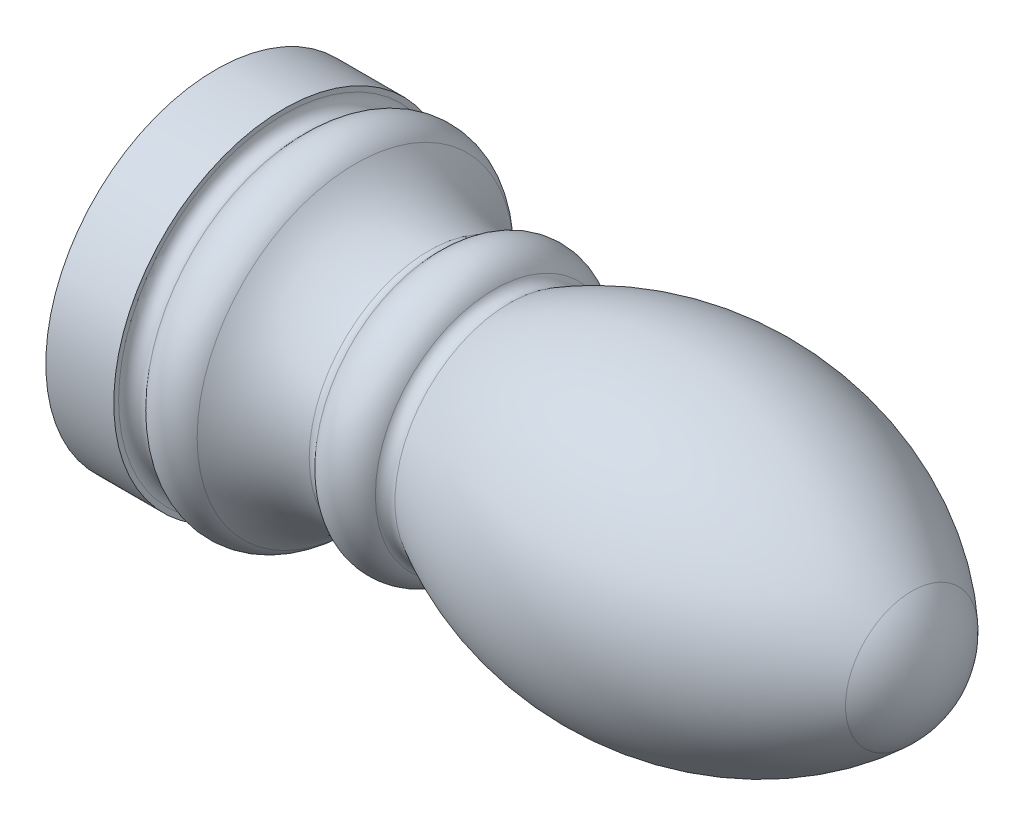
SolidWorks part; units mm, degrees
material "6061-T6 (SS)"
ref_plane "Front" through (0, 0, 0) normal (0, 0, 1) x (1, 0, 0)
ref_plane "Top" through (0, 0, 0) normal (0, 1, 0) x (1, 0, 0)
ref_plane "Right" through (0, 0, 0) normal (1, 0, 0) x (0, 0, -1)
sketch "Sketch1" plane through (0, 0, 0) normal (0, 0, 1) x (1, 0, 0)
  line L0 (0, 0) -> (0, -7.5)
  line L1 (0, -7.5) -> (3, -7.5)
  line L2 (0, 0) -> (-8.1317, 0) construction
  line L3 (0, 0) -> (32, 0)
  line L4 (3, -7.5) -> (3, -7.2856)
  line L6 (3.883, -6.9642) -> (1.6828, -4.3421) construction
  line L8 (9.8509, -5.4642) -> (8.7603, -4.1644) construction
  arc A0 (3, -7.2856) -> (3.883, -6.9642) centre (3.5, -7.2856) cw
  arc A1 (3.883, -6.9642) -> (6.1649, -6.9832) centre (5.0321, -6) ccw
  arc A3 (9.8509, -5.4642) -> (12.299, -5.25) centre (11, -4.5) ccw
  arc A5 (12.9766, -5.0639) -> (12.299, -5.25) centre (12.7321, -5.5) ccw
  arc A6 (6.1649, -6.9832) -> (9.4154, -5.2883) centre (9.941, -10.2606) cw
  arc A7 (9.4154, -5.2883) -> (9.8509, -5.4642) centre (9.4679, -5.7856) cw
  arc A8 (32, 0) -> (30.7292, -2.9243) centre (28, 0) cw
  arc A9 (30.7292, -2.9243) -> (12.9766, -5.0639) centre (20.3886, 8.1556) cw
  dimension "D2" = 4
  dimension "D6" = 14
  dimension "D7" = 1.5
  dimension "D4" = 0.5
  dimension "D8" = 40
  dimension "D10" = 1.5
  dimension "D11" = 5
  dimension "D9" = 12
  dimension "D13" = 10
  dimension "D1" = 15
  dimension "D3" = 32
  dimension "D5" = 3
  dimension "D12" = 21
revolve "Revolve1" add sketch "Sketch1" angle 360 about L2
sketch "Sketch2" plane through (0, 0, 0) normal (0, 1, 0) x (1, 0, 0)
  line L0 (31.6383, 2) -> (21.4481, 2)
  line L1 (0, 0) -> (-2.4973, 0) construction
  line L2 (0, 7.5) -> (0, -7.5) construction
  arc A0 (21.4481, 2) -> (14, 5.5877) centre (21.4481, 11.525) cw
  arc A1 (30.7292, 2.9243) -> (12.9766, 5.0639) centre (20.3886, -8.1556) ccw construction
  dimension "D3" = 19.05
  dimension "D1" = 4
  dimension "D2" = 14
extrude "Cut-Extrude1" [suppressed] cut sketch "Sketch2" against normal through all and the other way through all flip side to cut
mirror "Mirror1" [suppressed] about plane through (0, 0, 0) normal (0, 0, 1)
sketch "Sketch3" plane through (0, 0, 0) normal (0, 0, 1) x (1, 0, 0)
  line L0 (30.4335, 1.25) -> (31.7997, 1.25)
  line L2 (14, 5.5877) -> (19.3859, 1.8165)
  line L4 (0, 0) -> (8.1984, 0) construction
  line L5 (0, 7.5) -> (0, -7.5) construction
  arc A1 (30.7292, 2.9243) -> (12.9766, 5.0639) centre (20.3886, -8.1556) ccw construction
  arc A2 (22.0395, 3.8333) -> (24.3113, 4.8561) centre (23.218, 4.25) cw
  arc A3 (24.3113, 4.8561) -> (30.4335, 1.25) centre (30.4335, 8.25) ccw
  arc A4 (19.3859, 1.8165) -> (22.0395, 3.8333) centre (20.3896, 3.25) ccw
  arc A5 (30.7292, -2.9243) -> (30.7292, 2.9243) centre (28, 0) ccw construction
  dimension "D1" = 1.75
  dimension "D3" = 1.25
  dimension "D5" = 5.5
  dimension "D10" = 1.5
  dimension "D6" = 7
  dimension "D2" = 35
  dimension "D4" = 14
  dimension "D7" = 1.25
extrude "Cut-Extrude2" [suppressed] cut sketch "Sketch3" against normal through all and the other way through all
sketch "Sketch4" [suppressed] plane through (0, 0, 0) normal (0, 0, 1) x (1, 0, 0)
  line L1 (30, 1.2634) -> (32, 1.2634)
  line L2 (30, 1.2634) -> (30, -0.5)
  line L3 (30, -0.5) -> (32, -0.5)
  line L4 (32, 1.2634) -> (32, -0.5)
  arc A0 (24.3113, 4.8561) -> (30.4335, 1.25) centre (30.4335, 8.25) ccw construction
  arc A1 (30.7292, -2.9243) -> (31.7997, 1.25) centre (28, 0) ccw construction
  dimension "D1" = 0.5
  dimension "D2" = 2
extrude "Cut-Extrude3" [suppressed] cut sketch "Sketch4" against normal through all both and the other way through all
sketch "Sketch5" [suppressed] plane through (0, 0, 0) normal (1, 0, 0) x (0, 0, -1)
  line L0 (9.7054, 5.6034) -> (0, 0) construction
  line L1 (0, 0) -> (-11.3484, 6.552) construction
  line L2 (0, 0) -> (0, 4.9906) construction
  line L3 (12.7332, 7.9288) -> (0, 0.5774)
  line L4 (0, 0.5774) -> (-12.7332, 7.9288)
  line L5 (6.2765, 13.6237) -> (0, 10)
  line L6 (0, 10) -> (-6.2765, 13.6237)
  arc A0 (-6.2765, 13.6237) -> (-12.7332, 7.9288) centre (0, 0) ccw
  circle A1 centre (0, 0) radius 10 construction
  arc A2 (12.7332, 7.9288) -> (6.2765, 13.6237) centre (0, 0) ccw
  dimension "D1" = 30
  dimension "D2" = 20
  dimension "D3" = 120
  dimension "D4" = 1
extrude "Boss-Extrude1" [suppressed] add sketch "Sketch5" along normal blind 18 from offset 2 separate body
combine bodies "Combine1" [suppressed] operation type add bodies to combine 113 108
pattern_circular "CirPattern1" [suppressed] count 3 over 360 of bodies 114
